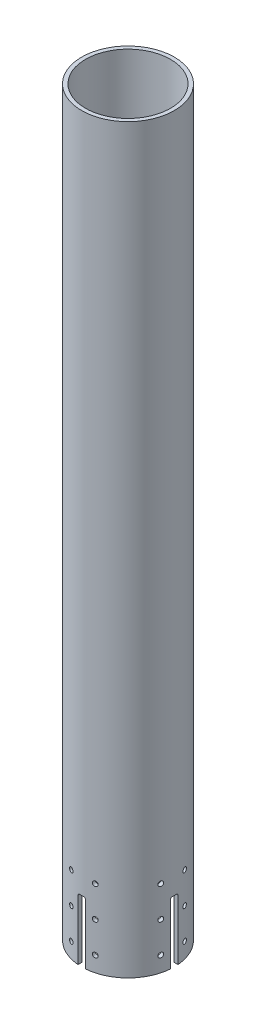
SolidWorks part; units mm, degrees
ref_plane "Front Plane" through (0, 0, 0) normal (0, 0, 1) x (1, 0, 0)
ref_plane "Top Plane" through (0, 0, 0) normal (0, 1, 0) x (1, 0, 0)
ref_plane "Right Plane" through (0, 0, 0) normal (1, 0, 0) x (0, 0, -1)
sketch "Sketch1" plane through (0, 0, 0) normal (0, 0, 1) x (1, 0, 0)
  line L0 (0, 0) -> (0, 304.8) construction
  line L1 (-19.05, 0) -> (-17.4625, 0)
  line L2 (-19.05, 0) -> (-19.05, 304.8)
  line L3 (-19.05, 304.8) -> (-17.4625, 304.8)
  line L4 (19.05, 0) -> (19.05, 304.8)
  line L5 (-17.4625, 0) -> (-17.4625, 304.8)
  line L6 (17.4625, 304.8) -> (17.4625, 0)
  line L7 (17.4625, 0) -> (19.05, 0)
  line L8 (17.4625, 304.8) -> (19.05, 304.8)
  dimension "D1" = 38.1
  dimension "12" = 304.8
  dimension "D2" = 1.5875
revolve "Revolve2" add sketch "Sketch1" angle 360 about L0 region at (-18.2563, 152.4, 0)
sketch "Sketch3" plane through (0, 0, 0) normal (0, 0, 1) x (1, 0, 0)
  line L0 (-1.5875, 0) -> (-1.5875, 25.4)
  line L1 (-19.05, 0) -> (19.05, 0) construction
  line L2 (-1.5875, 25.4) -> (1.5875, 25.4)
  line L3 (1.5875, 25.4) -> (1.5875, 0)
  line L4 (17.4625, 0) -> (19.05, 0) construction
  line L5 (0, 0) -> (0, 304.8) construction
  line L6 (1.5875, 0) -> (-1.5875, 0)
  dimension "D1" = 3.175
  dimension "D2" = 25.4
extrude "Cut-Extrude2" cut sketch "Sketch3" against normal blind 50.8 contours L6 L0 L2 L3
fillet "Fillet1" radius 0.7937 2 edges at (-1.5875, 25.4, -18.187) (1.5875, 25.4, -18.187)
pattern_circular "CirPattern1" count 4 over 360 about axis through (0, 0, 0) along (0, -1, 0) of "Cut-Extrude2", "Fillet1"
ref_plane "Plane2" through (0, 0, 19.05) normal (0, 0, 1) x (1, 0, 0)
sketch "Sketch9" plane through (0, 0, 0) normal (0, 1, 0) x (1, 0, 0)
  line L0 (0, 0) -> (4.9305, 18.4009)
  line L1 (0, 0) -> (0, 19.05) construction
  circle A0 centre (0, 0) radius 19.05 construction
  dimension "D1" = 15
ref_plane "Plane3" through (4.5196, 0, -16.8675) normal (-0.2588, 0, 0.9659) x (0.9659, 0, 0.2588)
sketch "Sketch6" plane through (4.7215, 0, -16.8134) normal (-0.2588, 0, 0.9659) x (0.9659, 0, 0.2588)
  line L0 (-18.135, 0) -> (3.1709, 0) construction
  line L3 (-0.209, 0) -> (-5.1395, 0) construction
  line L4 (-0.209, 0) -> (-5.1395, 0)
  circle A0 centre (-0.209, 6.35) radius 1
  circle A2 centre (-0.209, 19.05) radius 1
  circle A3 centre (-0.209, 31.75) radius 1
  dimension "D1" = 2
  dimension "D5" = 25.4
  dimension "D2" = 6.35
  dimension "D3" = 3
extrude "Cut-Extrude13" cut sketch "Sketch6" against normal blind 12.7 and the other way blind 12.7 contours A3 | A2 | A0 region at (4.5196, 6.35, -16.8675) region at (4.5196, 19.05, -16.8675) region at (4.5196, 31.75, -16.8675)
mirror "Mirror1" about plane through (0, 0, 0) normal (1, 0, 0) of "Cut-Extrude13"
pattern_circular "CirPattern3" count 4 over 360 about axis through (0, 0, 0) along (0, -1, 0) of "Mirror1", "Cut-Extrude13"
